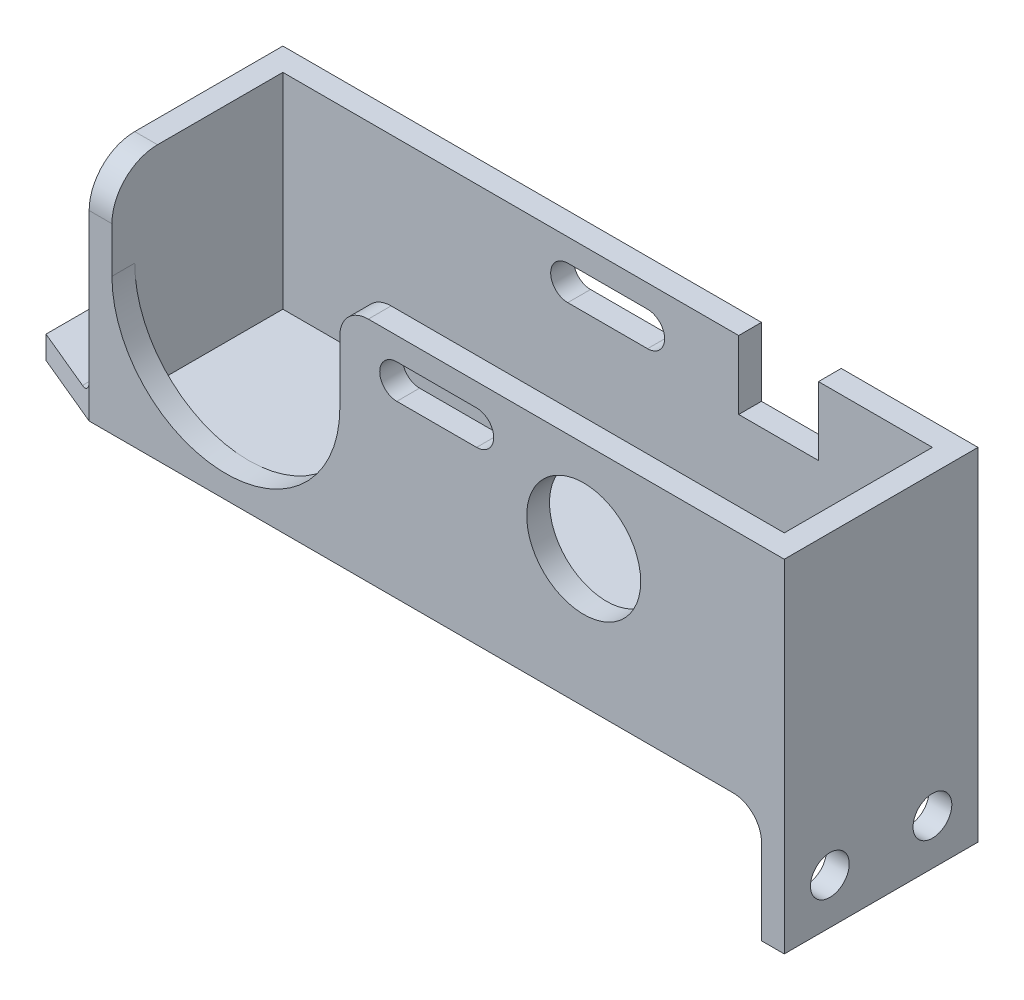
SolidWorks part; units mm, degrees
other "Markup1"
sketch "Sketch4" plane through (-28, -10, 6.5) normal (-0.9519, -0.1137, 0.2847) x (0.2678, 0.1434, 0.9527)
ref_plane "Front Plane" through (0, 0, 0) normal (0, 0, 1) x (1, 0, 0)
ref_plane "Top Plane" through (0, 0, 0) normal (0, 1, 0) x (1, 0, 0)
ref_plane "Right Plane" through (0, 0, 0) normal (1, 0, 0) x (0, 0, -1)
sketch "Sketch1" plane through (0, 0, 0) normal (0, 0, 1) x (1, 0, 0)
  line L0 (-28.5, 0) -> (28.5, 0) construction
  line L1 (-28.5, 9) -> (28.5, 9)
  line L2 (-28.5, -9) -> (28.5, -9)
  line L5 (-28.5, 9) -> (-28.5, -9)
  line L6 (0, 9) -> (0, -9) construction
  line L8 (28.5, 9) -> (28.5, -9)
  point P2 (0, 0)
  point P6 (0, 0)
  dimension "D1" = 57
  dimension "D2" = 18
extrude "Boss-Extrude1" add sketch "Sketch1" along normal mid plane 13
shell "Shell2" thickness 2 removed face at (0, 9, 0) outward yes
sketch "Sketch11" plane through (0, 0, 8.5) normal (0, 0, 1) x (1, 0, 0)
  line L0 (-28.5, 9) -> (-28.5, 1)
  line L1 (30.5, 9) -> (-30.5, 9) construction
  line L2 (-8.5, 1) -> (-8.5, 9)
  line L3 (-28.5, 9) -> (-8.5, 9)
  line L4 (-28.5, -9) -> (28.5, -9) construction
  arc A0 (-28.5, 1) -> (-8.5, 1) centre (-18.5, 1) ccw
  point P6 (0, 0)
  dimension "D1" = 10
extrude "lens cutout" cut sketch "Sketch11" against normal up to next
sketch "Sketch12" plane through (0, 0, 8.5) normal (0, 0, 1) x (1, 0, 0)
  line L2 (12.9, 1) -> (-18.5, 1) construction
  circle A0 centre (12.9, 1) radius 5
  arc A1 (-28.5, 1) -> (-8.5, 1) centre (-18.5, 1) ccw construction
  point P4 (0, 0)
  dimension "D2" = 10
  dimension "D1" = 31.4
extrude "power button hole" cut sketch "Sketch12" against normal up to next
sketch "Sketch13" plane through (0, 0, -8.5) normal (0, 0, -1) x (-1, 0, 0)
  line L2 (-30.5, 9) -> (30.5, 9) construction
  line L3 (-18.5, 9) -> (-11.5, 9)
  line L4 (-18.5, 9) -> (-18.5, 3)
  line L5 (-18.5, 3) -> (-11.5, 3)
  line L6 (-11.5, 9) -> (-11.5, 3)
  arc A0 (8.5, 1) -> (18.5, -9) centre (18.5, 1) ccw construction
  point P0 (18.5, 1)
  point P1 (0, 0)
  dimension "D1" = 30
  dimension "D2" = 2
  dimension "D3" = 7
extrude "Cut-Extrude3" cut sketch "Sketch13" against normal up to next
sketch "Sketch21" plane through (0, 0, 8.5) normal (0, 0, 1) x (1, 0, 0)
  line L0 (-3.5, 5.5) -> (3.5, 5.5) construction
  line L1 (-3.5, 7) -> (3.5, 7)
  line L2 (-3.5, 4) -> (3.5, 4)
  line L3 (30.5, 9) -> (-8.5, 9) construction
  arc A0 (-3.5, 7) -> (-3.5, 4) centre (-3.5, 5.5) ccw
  arc A1 (3.5, 4) -> (3.5, 7) centre (3.5, 5.5) ccw
  point P2 (0, 5.5)
  point P7 (-5, 5.5)
  point P8 (0, 5.7761)
  point P9 (0, 0)
  dimension "D1" = 3
  dimension "D2" = 10
  dimension "D3" = 2
extrude "Cut-Extrude4" cut sketch "Sketch21" against normal through all
fillet "Fillet4" radius 2.5 1 edges at (-8.5, 9, 7.5)
sketch "Sketch15" plane through (0, -11, 0) normal (0, -1, 0) x (1, 0, 0)
  line L0 (-30.5, 8.5) -> (-30.5, -8.5)
  line L1 (-30.5, -8.5) -> (-37, -11.2146)
  line L2 (-37, -11.2146) -> (-37, 5.7854)
  line L3 (-37, 5.7854) -> (-30.5, 8.5)
  dimension "D1" = 67.333
  dimension "D2" = 6.5
extrude "Boss-Extrude3" add sketch "Sketch15" against normal blind 2
hole_wizard "M3 Clearance Hole1" positions "Sketch16" profile "Sketch17" hole size "M3" standard "ANSI Metric" end condition through all
sketch "Sketch16" plane through (0, -9, 0) normal (0, 1, 0) x (1, 0, 0)
  line L0 (-33.75, 9.8573) -> (-33.75, -7.1427) construction
  line L1 (-37, 11.2146) -> (-30.5, 8.5) construction
  line L2 (-30.5, -8.5) -> (-37, -5.7854) construction
  line L6 (-33.75, 1.3573) -> (-37, 1.3573) construction
  line L7 (-37, -5.7854) -> (-37, 11.2146) construction
  point P16 (-33.75, 5.3573)
  point P18 (-33.75, -2.6427)
  point P21 (0, 0)
  point P22 (-33.75, 6.8041)
  dimension "D1" = 8
sketch "Sketch17" plane through (-33.75, -9, 2.6427) normal (1, 0, 0) x (0, 0, 1)
  line L0 (0, 0) -> (0, 2)
  line L1 (0, 2) -> (1.7, 2)
  line L2 (1.7, 2) -> (1.7, 0)
  line L5 (1.7, 0) -> (0, 0)
  line L11 (0, -6.35) -> (0, 107.95) construction
  dimension "Thru Hole Dia." = 3.4
  dimension "Thru Hole Depth" = 2
fillet "Fillet2" radius 1 1 edges at (-30.5, -9, 0)
sketch "Sketch18" plane through (0, -11, 0) normal (0, -1, 0) x (1, 0, 0)
  line L0 (-30.5, -8.5) -> (30.5, -8.5) construction
  line L1 (30.5, 8.5) -> (28.5, 8.5)
  line L2 (30.5, 8.5) -> (30.5, -8.5)
  line L3 (30.5, -8.5) -> (28.5, -8.5)
  line L4 (28.5, 8.5) -> (28.5, -8.5)
  dimension "D1" = 2
extrude "Boss-Extrude4" add sketch "Sketch18" along normal blind 10
hole_wizard "M3 Clearance Hole2" positions "Sketch19" profile "Sketch20" hole size "M3" standard "ANSI Metric" end condition through all
sketch "Sketch19" plane through (28.5, 0, 0) normal (-1, 0, 0) x (0, 0, 1)
  line L0 (0, -21) -> (0, -11) construction
  line L1 (8.5, -21) -> (-8.5, -21) construction
  line L2 (8.5, -11) -> (-8.5, -11) construction
  point P0 (-4.5, -17)
  point P2 (4.5, -17)
  point P13 (0, 0)
  dimension "D1" = 9
  dimension "D2" = 4
sketch "Sketch20" plane through (28.5, -17, -4.5) normal (0, 1, 0) x (0, 0, 1)
  line L0 (0, 0) -> (0, 2)
  line L1 (0, 2) -> (1.7, 2)
  line L2 (1.7, 2) -> (1.7, 0)
  line L5 (1.7, 0) -> (0, 0)
  line L11 (0, -6.35) -> (0, 107.95) construction
  dimension "Thru Hole Dia." = 3.4
  dimension "Thru Hole Depth" = 2
fillet "Fillet3" radius 2.5 1 edges at (28.5, -11, 0)
fillet "Fillet5" radius 4 1 edges at (-29.5, 9, 8.5)
equation "\"wallthickness\"= 2"
equation "\"D1@Boss-Extrude1\"=13"
equation "\"D1@Shell2\"=\"wallthickness\""
equation "\"D1@Boss-Extrude3\"=\"wallthickness\""
equation "\"D1@Sketch18\"=\"wallthickness\""
